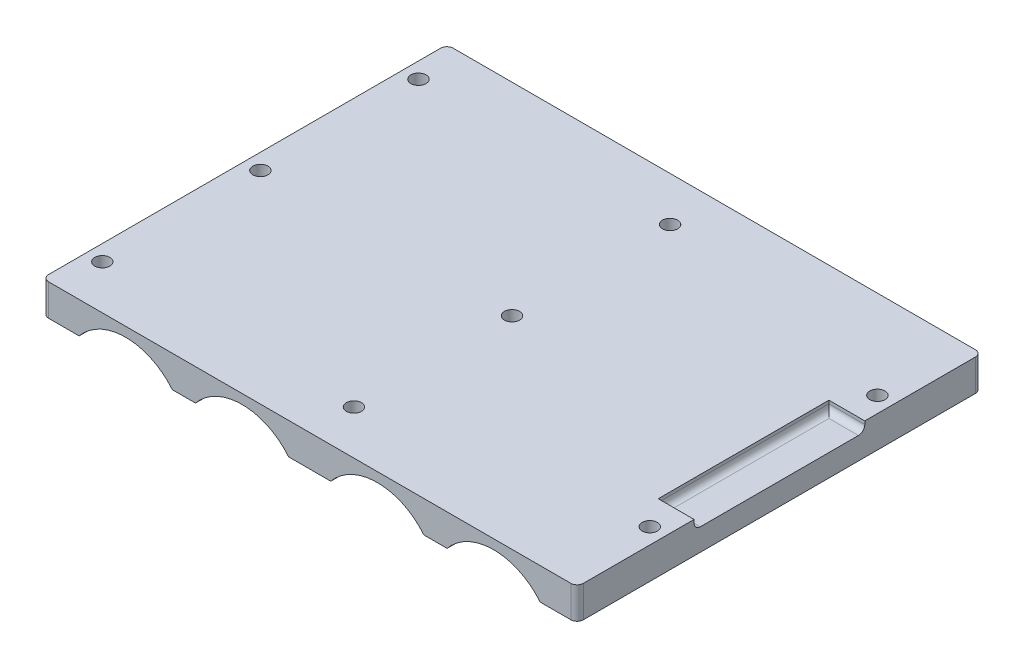
SolidWorks part; units mm, degrees
material "Windform GT"
ref_plane "Front Plane" through (0, 0, 0) normal (0, 0, 1) x (1, 0, 0)
ref_plane "Top Plane" through (0, 0, 0) normal (0, 1, 0) x (1, 0, 0)
ref_plane "Right Plane" through (0, 0, 0) normal (1, 0, 0) x (0, 0, -1)
sketch "Sketch2" plane through (0, 0, 0) normal (0, 0, 1) x (1, 0, 0)
  line L2 (3.3345, -5) -> (-3.3345, -5)
  line L3 (-18.0655, -5) -> (-21.7345, -5)
  line L4 (-36.4655, -5) -> (-42.3, -5)
  line L5 (-42.3, -5) -> (-42.3, 0)
  line L7 (36.4655, -5) -> (42.3, -5)
  line L9 (18.0655, -5) -> (21.7345, -5)
  line L11 (42.3, -5) -> (42.3, 0)
  line L12 (-42.3, 0) -> (42.3, 0)
  line L13 (0, -55) -> (0, 55) construction
  line L14 (25.85, 0) -> (-25.85, 0) construction
  arc A0 (-3.3345, -5) -> (-18.0655, -5) centre (-10.7, -11) ccw
  arc A1 (-21.7345, -5) -> (-36.4655, -5) centre (-29.1, -11) ccw
  arc A2 (21.7345, -5) -> (36.4655, -5) centre (29.1, -11) cw
  arc A3 (3.3345, -5) -> (18.0655, -5) centre (10.7, -11) cw
  point P3 (0, 0)
  dimension "D1" = 9.5
  dimension "D2" = 13.2
  dimension "D3" = 11
  dimension "D4" = 18.4
  dimension "D5" = 18.4
  dimension "D6" = 5
  dimension "D7" = 21.4
extrude "Boss-Extrude1" add sketch "Sketch2" along normal mid plane 64 contours A0 L3 A1 L4 L5 L12 L11 L7 A2 L9 A3 L2
hole_wizard "M2 Clearance Hole1" positions "Sketch7" profile "Sketch8" hole size "M2" standard "ANSI Metric" end condition through all
sketch "Sketch7" plane through (0, -5, 0) normal (0, -1, 0) x (-1, 0, 0)
  line L2 (39.8, 25) -> (0, 25) construction
  line L3 (39.8, 25) -> (39.8, -25) construction
  line L4 (39.8, -25) -> (0, -25) construction
  line L5 (0, 25) -> (0, -25) construction
  line L10 (42.3, -32) -> (42.3, 32) construction
  line L12 (-42.3, -32) -> (-42.3, 32) construction
  line L13 (-36.4655, 32) -> (-42.3, 32) construction
  line L14 (-36.4655, -32) -> (-42.3, -32) construction
  line L15 (0, 55) -> (0, -55) construction
  point P0 (0, 25)
  point P2 (0, 0)
  point P4 (0, -25)
  point P6 (39.8, -25)
  point P8 (39.8, 0)
  point P10 (39.8, 25)
  point P291 (-39.8, -18)
  point P296 (-39.8, 18)
  dimension "D1" = 2.5
  dimension "D3" = 50
  dimension "D5" = 50
  dimension "D6" = 2.5
  dimension "D7" = 2.5
  dimension "D8" = 14
  dimension "D9" = 14
sketch "Sketch8" plane through (0, -5, -25) normal (1, 0, 0) x (0, 0, -1)
  line L0 (0, 0) -> (0, 5)
  line L1 (0, 5) -> (1.2, 5)
  line L2 (1.2, 5) -> (1.2, 0)
  line L5 (1.2, 0) -> (0, 0)
  line L11 (0, -6.35) -> (0, 107.95) construction
  dimension "Thru Hole Dia." = 2.4
  dimension "Thru Hole Depth" = 5
fillet "Fillet1" radius 1 4 edges at (-42.3, -2.5, -32) (42.3, -2.5, -32) (-42.3, -2.5, 32) (42.3, -2.5, 32)
sketch "Sketch9" plane through (0, 0, 0) normal (0, 1, 0) x (1, 0, 0)
  line L0 (42.3, -31) -> (42.3, 31) construction
  line L1 (42.3, -13.5) -> (36.63, -13.5)
  line L2 (42.3, -13.5) -> (42.3, 13.5)
  line L3 (42.3, 13.5) -> (36.63, 13.5)
  line L4 (36.63, -13.5) -> (36.63, 13.5)
  point P6 (42.3, 0)
  point P7 (42.3, 0)
  dimension "D1" = 5.67
  dimension "D2" = 27
extrude "Cut-Extrude1" cut sketch "Sketch9" against normal blind 1.5
fillet "Fillet2" radius 1 3 edges at (39.465, -1.5, -13.5) (36.63, -1.5, 0) (39.465, -1.5, 13.5)
